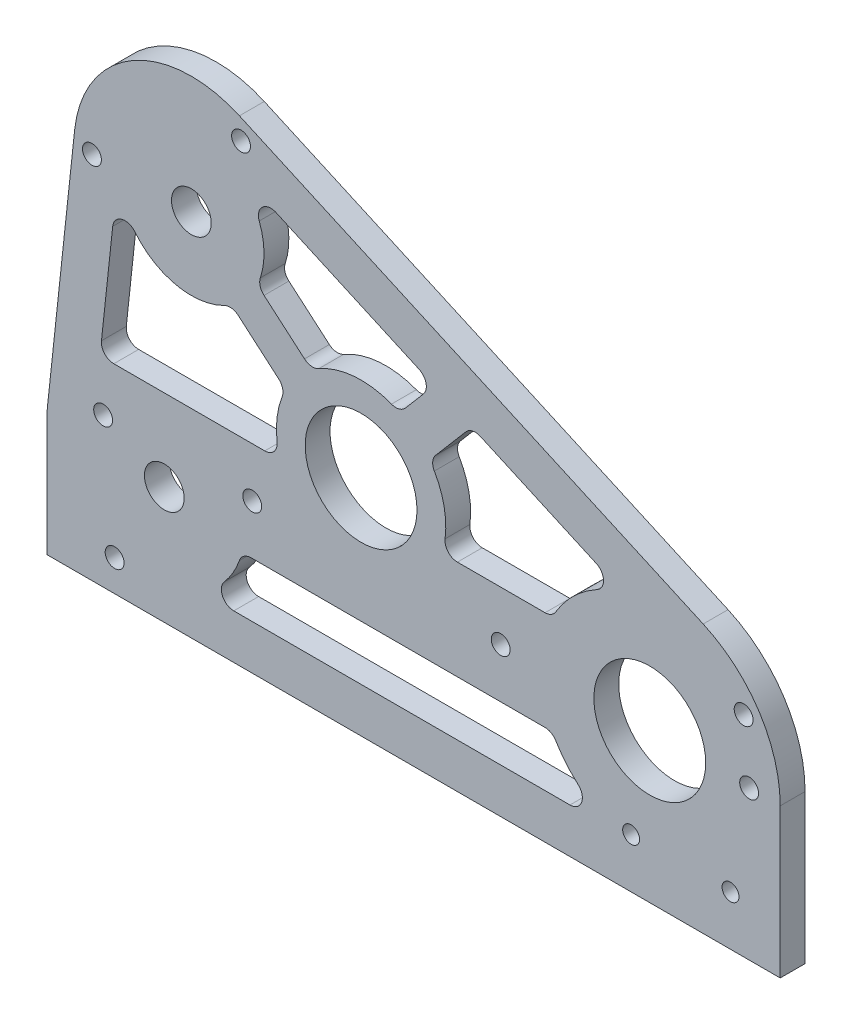
SolidWorks part; units mm, degrees
material "6061-T6 (SS)"
ref_plane "Front Plane" through (0, 0, 0) normal (0, 0, 1) x (1, 0, 0)
ref_plane "Top Plane" through (0, 0, 0) normal (0, 1, 0) x (1, 0, 0)
ref_plane "Right Plane" through (0, 0, 0) normal (1, 0, 0) x (0, 0, -1)
sketch "Sketch1" plane through (0, 0, 0) normal (0, 0, 1) x (1, 0, 0)
  line L0 (-50.2878, -27.1526) -> (0, 0) construction
  line L1 (0, 0) -> (-43.3772, 37.2094) construction
  line L2 (-80.2852, -57.15) -> (107.1178, -57.15)
  line L3 (87.4344, 11.3631) -> (-31.0912, 64.5754)
  line L4 (-80.1137, -23.9502) -> (-73.2032, 40.4118)
  line L5 (-80.2852, -27.1526) -> (-80.2852, -57.15)
  line L6 (107.1178, -57.15) -> (107.1178, -19.05)
  line L7 (-80.2852, -57.15) -> (142.6901, -57.15) construction
  line L8 (-80.2852, -57.15) -> (-80.2852, -19.05) construction
  line L9 (-80.2852, -19.05) -> (142.6901, -19.05) construction
  line L10 (142.6901, -57.15) -> (142.6901, -19.05) construction
  line L11 (-50.2878, 2.8448) -> (-49.7454, 7.8958) construction
  line L13 (-68.7772, 37.2094) -> (-56.0772, 15.2124) construction
  line L14 (-56.0772, 15.2124) -> (-30.6772, 15.2124) construction
  line L15 (-30.6772, 15.2124) -> (-17.9772, 37.2094) construction
  line L16 (-17.9772, 37.2094) -> (-30.6772, 59.2065) construction
  line L17 (-30.6772, 59.2065) -> (-56.0772, 59.2065) construction
  line L18 (-56.0772, 59.2065) -> (-68.7772, 37.2094) construction
  line L19 (-37.5878, -49.1496) -> (-24.8878, -27.1526) construction
  line L20 (-24.8878, -27.1526) -> (-37.5878, -5.1556) construction
  line L21 (-37.5878, -5.1556) -> (-62.9878, -5.1556) construction
  line L22 (-62.9878, -5.1556) -> (-75.6878, -27.1526) construction
  line L23 (-75.6878, -27.1526) -> (-62.9878, -49.1496) construction
  line L24 (-62.9878, -49.1496) -> (-37.5878, -49.1496) construction
  line L26 (73.7803, -19.05) -> (97.7695, -3.5241) construction
  line L27 (107.1178, -57.15) -> (94.4178, -57.15) construction
  line L28 (107.1178, -57.15) -> (107.1178, -44.45) construction
  line L29 (107.1178, -44.45) -> (94.4178, -44.45) construction
  line L30 (94.4178, -57.15) -> (94.4178, -44.45) construction
  line L31 (97.7695, -3.5241) -> (101.7677, -0.9365) construction
  circle A0 centre (0, 0) radius 14.2875
  circle A1 centre (-43.3772, 37.2094) radius 12.7
  circle A2 centre (-50.2878, -27.1526) radius 12.7
  arc A4 (-73.2032, 40.4118) -> (-31.0912, 64.5754) centre (-43.3772, 37.2094) cw
  circle A8 centre (-50.2878, -27.1526) radius 29.9974 construction
  arc A10 (-80.2852, -27.1526) -> (-80.1137, -23.9502) centre (-50.2878, -27.1526) cw
  circle A11 centre (73.7803, -19.05) radius 14.2875
  arc A12 (87.4344, 11.3631) -> (107.1178, -19.05) centre (73.7803, -19.05) cw
  circle A13 centre (-43.3772, 37.2094) radius 29.9974 construction
  circle A14 centre (0, 0) radius 52.07 construction
  circle A16 centre (-43.3772, 37.2094) radius 25.4 construction
  circle A17 centre (-43.3772, 37.2094) radius 21.997 construction
  circle A18 centre (-68.7772, 37.2094) radius 2.413
  circle A19 centre (-17.9772, 37.2094) radius 2.413
  circle A20 centre (-56.0772, 59.2065) radius 2.413
  circle A21 centre (-30.6772, 59.2065) radius 2.413
  circle A22 centre (-56.0772, 15.2124) radius 2.413
  circle A23 centre (-30.6772, 15.2124) radius 2.413
  circle A24 centre (-50.2878, -27.1526) radius 25.4 construction
  circle A25 centre (-50.2878, -27.1526) radius 21.997 construction
  circle A26 centre (-62.9878, -5.1556) radius 2.413
  circle A27 centre (-75.6878, -27.1526) radius 2.413
  circle A28 centre (-62.9878, -49.1496) radius 2.413
  circle A29 centre (-37.5878, -49.1496) radius 2.413
  circle A30 centre (-24.8878, -27.1526) radius 2.413
  circle A31 centre (-37.5878, -5.1556) radius 2.413
  circle A33 centre (94.4178, -44.45) radius 2.159
  circle A34 centre (97.7695, -3.5241) radius 2.413
  circle A35 centre (97.7695, -3.5241) radius 4.7625 construction
  circle A37 centre (69.0178, -44.45) radius 2.159
  point P13 (-80.2852, -27.1526)
  dimension "D1" = 25.4
  dimension "D2" = 28.575
  dimension "D4" = 38.1
  dimension "D5" = 29.9974
  dimension "D6" = 59.9948
  dimension "D9" = 19.05
  dimension "D11" = 104.14
  dimension "D12" = 50.8
  dimension "D13" = 4.826
  dimension "D14" = 9.525
  dimension "D15" = 12.7
  dimension "D16" = 4.318
  dimension "D3" = 57.15
  dimension "D7" = 76.2
  dimension "D8" = 57.15
  dimension "D10" = 5.08
  dimension "D17" = 25.4
extrude "Boss-Extrude1" add sketch "Sketch1" along normal blind 6.35
sketch "Sketch2" plane through (0, 0, 6.35) normal (0, 0, 1) x (1, 0, 0)
  circle A0 centre (-56.0772, 59.2065) radius 2.413
  circle A1 centre (-17.9772, 37.2094) radius 2.6856
  circle A2 centre (-30.6772, 15.2124) radius 7.6914
  circle A3 centre (-56.0772, 15.2124) radius 5.0345
  circle A4 centre (-75.6878, -27.1526) radius 2.413
  circle A5 centre (-75.6878, -27.1526) radius 2.413 construction
  circle A6 centre (-37.5878, -49.1496) radius 5.9207
  circle A7 centre (-24.8878, -27.1526) radius 7.7344
  circle A8 centre (-37.5878, -5.1556) radius 5.6219
  circle A9 centre (-62.9878, -5.1556) radius 3.6056
extrude "Boss-Extrude2" add sketch "Sketch2" against normal up to surface (6.35 mm away) up to face at (71.1768, -44.45, 0)
sketch "Sketch3" plane through (0, 0, 6.35) normal (0, 0, 1) x (1, 0, 0)
  line L0 (73.7803, -19.05) -> (-79.5876, -19.05) construction
  line L1 (-73.2032, 40.4118) -> (-80.1137, -23.9502) construction
  line L2 (73.7803, -19.05) -> (107.1178, -19.05) construction
  circle A0 centre (-65.9197, -19.05) radius 2.413
  circle A1 centre (-27.8197, -19.05) radius 2.413
  circle A2 centre (99.1803, -19.05) radius 2.413
  circle A3 centre (35.6803, -19.05) radius 2.413
  dimension "D1" = 4.826
  dimension "D3" = 38.1
  dimension "D2" = 139.7
  dimension "D4" = 25.4
  dimension "D5" = 38.1
extrude "Cut-Extrude1" cut sketch "Sketch3" against normal through all
sketch "Sketch4" plane through (0, 0, 6.35) normal (0, 0, 1) x (1, 0, 0)
  circle A0 centre (-50.2878, -27.1526) radius 12.7
  circle A1 centre (-50.2878, -27.1526) radius 5.08
  circle A2 centre (-43.3772, 37.2094) radius 12.7
  circle A3 centre (-43.3772, 37.2094) radius 5.08
  dimension "D1" = 10.16
extrude "Boss-Extrude3" add sketch "Sketch4" against normal up to surface (6.35 mm away) up to face at (-63.5067, -19.05, 0)
sketch "Sketch5" [suppressed] plane through (0, 0, 6.35) normal (0, 0, 1) x (1, 0, 0)
  line L0 (0, 0) -> (38.5155, 20.7963) construction
  line L1 (-2.4136, 4.47) -> (36.102, 25.2663) construction
  line L2 (0, 0) -> (14.2312, 31.6987)
  line L3 (4.6344, -2.0806) -> (18.8656, 29.6181)
  line L4 (-4.6344, 2.0806) -> (9.5968, 33.7794)
  line L5 (-50.2878, -27.1526) -> (0, 0)
  line L6 (0, 0) -> (16.4066, 8.8587)
  line L7 (73.7803, -19.05) -> (0, 0)
  line L8 (0, 0) -> (-43.3772, 37.2094)
  line L9 (-47.8742, -31.6226) -> (2.4136, -4.47)
  line L10 (-68.8552, -45.72) -> (95.6878, -45.72)
  line L11 (-68.8552, -27.1526) -> (-68.8552, -45.72)
  line L12 (-61.8385, 39.1916) -> (-68.7491, -25.1704)
  line L13 (95.6878, -45.72) -> (95.6878, -19.05)
  line L14 (82.753, 0.9357) -> (-35.7726, 54.1481)
  line L15 (-68.8552, -45.72) -> (95.6878, -45.72)
  line L16 (-68.8552, -27.1526) -> (-68.8552, -45.72)
  line L17 (-61.8385, 39.1916) -> (-68.7491, -25.1704)
  line L18 (95.6878, -45.72) -> (95.6878, -19.05)
  line L19 (82.753, 0.9357) -> (-35.7726, 54.1481)
  line L20 (3.3075, 3.8558) -> (-40.0697, 41.0652)
  line L21 (2.4136, -4.47) -> (16.7287, 3.2593)
  line L22 (75.0503, -14.1313) -> (1.27, 4.9187)
  line L23 (-52.7013, -22.6826) -> (-2.4136, 4.47)
  line L24 (-3.3075, -3.8558) -> (-46.6847, 33.3537)
  line L25 (-2.4136, 4.47) -> (13.2112, 12.9065)
  line L26 (72.5103, -23.9687) -> (-1.27, -4.9187)
  line L27 (2.4136, -4.47) -> (40.9291, 16.3262) construction
  line L28 (0, 0) -> (13.4163, -45.72)
  line L29 (-4.8745, -1.4304) -> (8.5419, -47.1504)
  line L30 (4.8745, 1.4304) -> (20.8281, -52.9361)
  line L31 (4.8745, 1.4304) -> (18.2908, -44.2896) construction
  circle A3 centre (73.7803, -19.05) radius 27.94
  circle A4 centre (-43.3772, 37.2094) radius 31.75
  circle A5 centre (-50.2878, -27.1526) radius 31.75
  arc A6 (-68.7491, -25.1704) -> (-68.8552, -27.1526) centre (-50.2878, -27.1526) ccw
  arc A7 (-35.7726, 54.1481) -> (-61.8385, 39.1916) centre (-43.3772, 37.2094) ccw
  arc A8 (95.6878, -19.05) -> (82.753, 0.9357) centre (73.7803, -19.05) ccw
  arc A9 (-68.7491, -25.1704) -> (-68.8552, -27.1526) centre (-50.2878, -27.1526) ccw
  arc A10 (-35.7726, 54.1481) -> (-61.8385, 39.1916) centre (-43.3772, 37.2094) ccw
  arc A11 (95.6878, -19.05) -> (82.753, 0.9357) centre (73.7803, -19.05) ccw
  circle A12 centre (0, 0) radius 21.0264
  dimension "D2" = 63.5
  dimension "D3" = 5.08
  dimension "D9" = 55.88
  dimension "D1" = 11.43
  dimension "D4" = 5.08
  dimension "D5" = 5.08
  dimension "D6" = 5.08
  dimension "D7" = 5.08
  dimension "D8" = 5.08
extrude "Cut-Extrude2" [suppressed] cut sketch "Sketch5" against normal blind 187.706 contours A12 L9 A5 L15 L29 | A12 L30 L15 A3 L26 | A12 L22 A3 L19 L21 | A12 L25 L19 A4 L20
fillet "Fillet1" [suppressed] radius 3.175
sketch "Sketch6" plane through (0, 0, 6.35) normal (0, 0, 1) x (1, 0, 0)
  line L0 (-50.2878, -27.1526) -> (0, 0)
  line L1 (-47.8742, -31.6226) -> (2.4136, -4.47)
  line L3 (95.6878, -19.05) -> (-79.5876, -19.05) construction
  line L6 (-43.3772, 37.2094) -> (0, 0)
  line L7 (0, 0) -> (35.6803, -19.05)
  line L8 (35.6803, -19.05) -> (73.7803, -19.05)
  line L9 (35.6803, -13.97) -> (73.7803, -13.97)
  line L11 (-68.8552, -45.72) -> (95.6878, -45.72)
  line L12 (-68.8552, -27.1526) -> (-68.8552, -45.72)
  line L13 (-61.8385, 39.1916) -> (-68.7491, -25.1704)
  line L14 (95.6878, -45.72) -> (95.6878, -19.05)
  line L15 (82.753, 0.9357) -> (-35.7726, 54.1481)
  line L16 (-68.8552, -45.72) -> (95.6878, -45.72)
  line L17 (-68.8552, -27.1526) -> (-68.8552, -45.72)
  line L18 (-61.8385, 39.1916) -> (-68.7491, -25.1704)
  line L19 (95.6878, -45.72) -> (95.6878, -19.05)
  line L20 (82.753, 0.9357) -> (-35.7726, 54.1481)
  line L22 (35.6803, -24.13) -> (73.7803, -24.13)
  line L23 (-2.3926, -4.4813) -> (33.2877, -23.5313)
  line L24 (-46.6847, 33.3537) -> (-3.3075, -3.8558)
  line L25 (-40.0697, 41.0652) -> (3.3075, 3.8558)
  line L26 (0, 0) -> (23.4902, 27.5419)
  line L27 (3.8651, -3.2965) -> (33.1087, 30.9911)
  line L28 (-3.8651, 3.2965) -> (19.6251, 30.8384)
  line L29 (3.8651, -3.2965) -> (27.3553, 24.2454) construction
  line L30 (-73.2032, 40.4118) -> (-80.1137, -23.9502) construction
  line L31 (95.6878, -6.35) -> (-79.5876, -6.35)
  line L32 (95.6878, -31.75) -> (-79.5876, -31.75)
  circle A3 centre (0, 0) radius 21.646
  circle A4 centre (73.7803, -19.05) radius 27.94
  circle A5 centre (-43.3772, 37.2094) radius 18.5674
  arc A6 (-68.7491, -25.1704) -> (-68.8552, -27.1526) centre (-50.2878, -27.1526) ccw
  arc A7 (-35.7726, 54.1481) -> (-61.8385, 39.1916) centre (-43.3772, 37.2094) ccw
  arc A8 (95.6878, -19.05) -> (82.753, 0.9357) centre (73.7803, -19.05) ccw
  arc A9 (-68.7491, -25.1704) -> (-68.8552, -27.1526) centre (-50.2878, -27.1526) ccw
  arc A10 (-35.7726, 54.1481) -> (-61.8385, 39.1916) centre (-43.3772, 37.2094) ccw
  arc A11 (95.6878, -19.05) -> (82.753, 0.9357) centre (73.7803, -19.05) ccw
  circle A12 centre (-50.2878, -27.1526) radius 20.32
  dimension "D2" = 40.64
  dimension "D4" = 55.88
  dimension "D1" = 11.43
  dimension "D3" = 5.08
  dimension "D5" = 5.08
  dimension "D6" = 5.08
  dimension "D7" = 5.08
  dimension "D8" = 5.08
  dimension "D9" = 5.08
  dimension "D10" = 5.08
  dimension "D11" = 12.7
  dimension "D12" = 12.7
extrude "Cut-Extrude3" cut sketch "Sketch6" against normal blind 187.706 contours A12 L16 A4 L32 | A4 L20 L27 A3 L31 | A5 L18 L31 A3 L24 | A5 L25 A3 L28 L20 region at (-44.8258, 7.3397, 6.35) region at (10.3043, -39.0728, 6.35) region at (-8.131, 31.9379, 6.35) region at (37.7896, 7.4199, 6.35)
fillet "Fillet2" radius 3.175 19 edges at (48.8935, -31.75, 3.175) (65.4524, -45.72, 3.175) (-42.0322, -45.72, 3.175) (-30.4947, -31.75, 3.175) (18.6622, 29.7095, 3.175) (9.7892, 19.306, 3.175) (-12.6631, 17.5555, 3.175) (-26.5147, 29.4375, 3.175) (-35.7726, 54.1481, 3.175) (-19.2781, 9.844, 3.175) (-66.7283, -6.35, 3.175) (-61.8385, 39.1916, 3.175) (-33.1297, 21.726, 3.175) (20.6936, -6.35, 3.175) (17.5194, 12.7129, 3.175) (28.3182, 25.3743, 3.175) (66.9333, 8.038, 3.175) (48.8935, -6.35, 3.175) (-20.6936, -6.35, 3.175)
